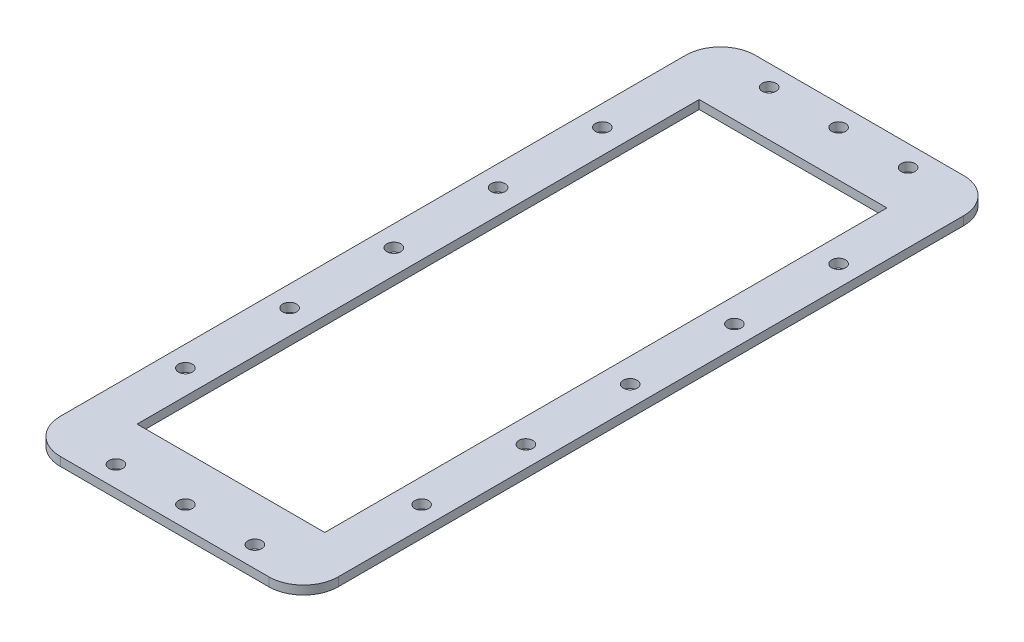
SolidWorks part; units mm, degrees
material "Thornel Mat VMA"
ref_plane "Front Plane" through (0, 0, 0) normal (0, 0, 1) x (1, 0, 0)
ref_plane "Top Plane" through (0, 0, 0) normal (0, 1, 0) x (1, 0, 0)
ref_plane "Right Plane" through (0, 0, 0) normal (1, 0, 0) x (0, 0, -1)
sketch "Sketch1" plane through (0, 0, 0) normal (0, 1, 0) x (1, 0, 0)
  line L0 (-157.6996, 42.9503) -> (197.9004, 42.9503) construction
  line L1 (-30.6996, 42.9503) -> (70.9004, 42.9503)
  line L2 (-30.6996, 42.9503) -> (-30.6996, -211.0497)
  line L3 (-30.6996, -211.0497) -> (70.9004, -211.0497)
  line L4 (70.9004, 42.9503) -> (70.9004, -211.0497)
  line L5 (-157.6996, -211.0497) -> (197.9004, -211.0497) construction
  dimension "D1" = 127
  dimension "D2" = 127
  dimension "D3" = 101.6
  dimension "D4" = 254
extrude "Boss-Extrude1" add sketch "Sketch1" along normal blind 3.175
sketch "Sketch2" plane through (0, 3.175, 0) normal (0, 1, 0) x (1, 0, 0)
  line L0 (20.1004, 42.9503) -> (20.1004, -50.0615) construction
  line L1 (70.9004, 42.9503) -> (-30.6996, 42.9503) construction
  line L2 (70.9004, -84.0497) -> (-81.795, -84.0497) construction
  line L3 (70.9004, -211.0497) -> (70.9004, 42.9503) construction
  line L4 (-30.6996, 42.9503) -> (-30.6996, -211.0497) construction
  circle A0 centre (-5.2996, 35.3303) radius 2.54
  circle A1 centre (20.1004, 35.3303) radius 2.54
  circle A2 centre (45.5004, 35.3303) radius 2.54
  circle A3 centre (-23.0796, -84.0497) radius 2.54
  circle A5 centre (-23.0796, -45.9497) radius 2.54
  circle A6 centre (-23.0796, -7.8497) radius 2.54
  circle A7 centre (63.2804, -7.8497) radius 2.54
  circle A8 centre (63.2804, -45.9497) radius 2.54
  circle A10 centre (63.2804, -84.0497) radius 2.54
  circle A12 centre (63.2804, -122.1497) radius 2.54
  circle A13 centre (63.2804, -160.2497) radius 2.54
  circle A14 centre (-23.0796, -160.2497) radius 2.54
  circle A15 centre (-23.0796, -122.1497) radius 2.54
  circle A17 centre (45.5004, -203.4297) radius 2.54
  circle A18 centre (20.1004, -203.4297) radius 2.54
  circle A19 centre (-5.2996, -203.4297) radius 2.54
  dimension "D3" = 5.08
  dimension "D4" = 5.08
  dimension "D5" = 5.08
  dimension "D10" = 5.08
  dimension "D11" = 5.08
  dimension "D12" = 5.08
  dimension "D1" = 25.4
  dimension "D2" = 25.4
  dimension "D6" = 38.1
  dimension "D8" = 38.1
  dimension "D13" = 7.62
  dimension "D14" = 7.62
extrude "Cut-Extrude1" cut sketch "Sketch2" against normal through all
fillet "Fillet1" radius 12.7 4 edges at (-30.6996, 1.5875, 211.0497) (70.9004, 1.5875, 211.0497) (70.9004, 1.5875, -42.9503) (-30.6996, 1.5875, -42.9503)
ref_axis "Axis1" through (20.1004, 0, -42.9503) along (0, 0.0125, 0.9999)
ref_axis "Axis2" through (-30.6996, 0, 84.0497) along (0.9995, 0.0312, 0)
ref_point "Point1"
sketch "Sketch4" plane through (0, 3.175, 0) normal (0, 1, 0) x (1, 0, 0)
  line L1 (-14.2153, 18.6855) -> (54.4161, 18.6855)
  line L2 (-14.2153, 18.6855) -> (-14.2153, -186.7849)
  line L3 (-14.2153, -186.7849) -> (54.4161, -186.7849)
  line L4 (54.4161, 18.6855) -> (54.4161, -186.7849)
  line L5 (-14.2153, 18.6855) -> (54.4161, -186.7849) construction
  line L6 (-14.2153, -186.7849) -> (54.4161, 18.6855) construction
  point P0 (20.1004, -84.0497)
extrude "Cut-Extrude2" cut sketch "Sketch4" against normal through all
